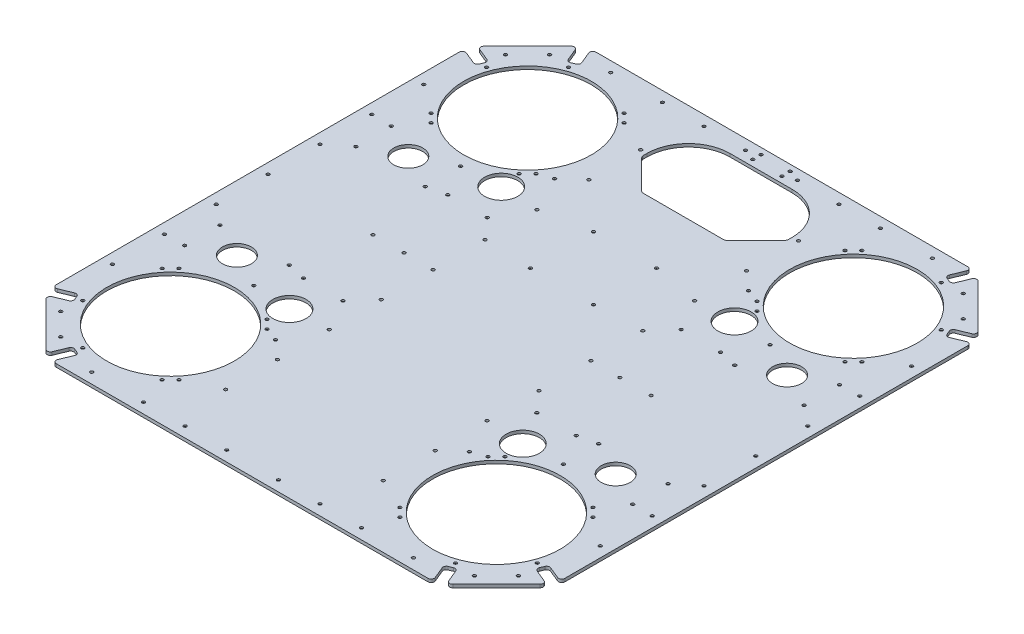
SolidWorks part; units mm, degrees
material "Thornel Mat VMA"
ref_plane "前视基准面" through (0, 0, 0) normal (0, 0, 1) x (1, 0, 0)
ref_plane "上视基准面" through (0, 0, 0) normal (0, 1, 0) x (1, 0, 0)
ref_plane "右视基准面" through (0, 0, 0) normal (1, 0, 0) x (0, 0, -1)
sketch "草图1" plane through (0, 0, 0) normal (0, 1, 0) x (1, 0, 0)
  line L1 (-245, -260) -> (245, -260)
  line L2 (-245, -260) -> (-245, 260)
  line L3 (-245, 260) -> (245, 260)
  line L4 (245, -260) -> (245, 260)
  line L5 (-245, -260) -> (245, 260) construction
  line L6 (-245, 260) -> (245, -260) construction
  point P0 (0, 0)
  dimension "D1" = 520
  dimension "D2" = 490
extrude "凸台-拉伸1" add sketch "草图1" along normal blind 3
sketch "草图2" plane through (0, 3, 0) normal (0, 1, 0) x (1, 0, 0)
  line L0 (-245, 0) -> (245, 0) construction
  line L1 (-245, 260) -> (-245, -260) construction
  line L2 (245, -260) -> (245, 260) construction
  line L3 (0, 260) -> (0, -260) construction
  line L4 (245, 260) -> (-245, 260) construction
  line L5 (-245, -260) -> (245, -260) construction
  line L6 (157, -172) -> (157, 172) construction
  line L7 (182.5, -82.5643) -> (215.9127, -65.5396) construction
  line L8 (145, -82.5643) -> (220, -82.5643) construction
  line L9 (157, -172) -> (203.669, -125.331) construction
  line L10 (157, -172) -> (199.424, -121.4411) construction
  line L11 (157, -172) -> (203.669, -218.669) construction
  line L12 (157, -172) -> (157, -260) construction
  line L13 (157, -172) -> (179.5733, -234.0197) construction
  line L14 (-157, -172) -> (-179.5733, -234.0197) construction
  line L15 (-157, -172) -> (-157, -260) construction
  line L16 (-157, -172) -> (-203.669, -218.669) construction
  line L17 (-157, -172) -> (-199.424, -121.4411) construction
  line L18 (-157, -172) -> (-203.669, -125.331) construction
  line L19 (-145, -82.5643) -> (-220, -82.5643) construction
  line L20 (-182.5, -82.5643) -> (-215.9127, -65.5396) construction
  line L21 (-157, -172) -> (-157, 172) construction
  line L22 (-182.5, 82.5643) -> (-215.9127, 65.5396) construction
  line L23 (-145, 82.5643) -> (-220, 82.5643) construction
  line L24 (-157, 172) -> (-203.669, 125.331) construction
  line L25 (-157, 172) -> (-199.424, 121.4411) construction
  line L26 (-157, 172) -> (-203.669, 218.669) construction
  line L27 (-157, 172) -> (-157, 260) construction
  line L28 (-157, 172) -> (-179.5733, 234.0197) construction
  line L29 (157, 172) -> (179.5733, 234.0197) construction
  line L30 (157, 172) -> (157, 260) construction
  line L31 (157, 172) -> (203.669, 218.669) construction
  line L32 (157, 172) -> (199.424, 121.4411) construction
  line L33 (157, 172) -> (203.669, 125.331) construction
  line L34 (145, 82.5643) -> (220, 82.5643) construction
  line L35 (182.5, 82.5643) -> (215.9127, 65.5396) construction
  line L36 (182.5, -45.0643) -> (182.5, -120.0643) construction
  circle A0 centre (157, -172) radius 61.5
  circle A1 centre (157, -172) radius 60 construction
  circle A2 centre (182.5, -82.5643) radius 33 construction
  circle A3 centre (182.5, -82.5643) radius 14
  circle A4 centre (182.5, -82.5643) radius 37.5 construction
  circle A5 centre (215.9127, -65.5396) radius 1.5
  circle A7 centre (215.9127, -99.5889) radius 1.5
  circle A9 centre (157, -172) radius 66 construction
  circle A10 centre (199.424, -121.4411) radius 1.5
  circle A11 centre (207.5589, -129.576) radius 1.5
  circle A14 centre (114.576, -222.5589) radius 1.5
  circle A15 centre (106.4411, -214.424) radius 1.5
  circle A16 centre (106.4411, -129.576) radius 1.5
  circle A17 centre (114.576, -121.4411) radius 1.5
  circle A18 centre (199.424, -222.5589) radius 1.5 [skipped]
  circle A19 centre (207.5589, -214.424) radius 1.5 [skipped]
  circle A20 centre (179.5733, -234.0197) radius 1.5
  circle A21 centre (219.0197, -194.5733) radius 1.5
  circle A22 centre (-157, -172) radius 66 construction
  circle A23 centre (-182.5, -82.5643) radius 37.5 construction
  circle A24 centre (-182.5, -82.5643) radius 33 construction
  circle A25 centre (-157, -172) radius 60 construction
  circle A26 centre (-219.0197, -194.5733) radius 1.5
  circle A27 centre (-179.5733, -234.0197) radius 1.5
  circle A28 centre (-114.576, -121.4411) radius 1.5
  circle A29 centre (-106.4411, -129.576) radius 1.5
  circle A30 centre (-106.4411, -214.424) radius 1.5
  circle A31 centre (-114.576, -222.5589) radius 1.5
  circle A32 centre (-207.5589, -129.576) radius 1.5
  circle A33 centre (-199.424, -121.4411) radius 1.5
  circle A35 centre (-215.9127, -99.5889) radius 1.5
  circle A37 centre (-215.9127, -65.5396) radius 1.5
  circle A38 centre (-182.5, -82.5643) radius 14
  circle A39 centre (-157, -172) radius 61.5
  circle A40 centre (-157, 172) radius 60 construction
  circle A41 centre (-182.5, 82.5643) radius 33 construction
  circle A42 centre (-182.5, 82.5643) radius 37.5 construction
  circle A43 centre (-157, 172) radius 66 construction
  circle A44 centre (157, 172) radius 66 construction
  circle A45 centre (182.5, 82.5643) radius 37.5 construction
  circle A46 centre (182.5, 82.5643) radius 33 construction
  circle A47 centre (157, 172) radius 60 construction
  circle A48 centre (-157, 172) radius 61.5
  circle A49 centre (-182.5, 82.5643) radius 14
  circle A50 centre (-215.9127, 65.5396) radius 1.5
  circle A52 centre (-215.9127, 99.5889) radius 1.5
  circle A54 centre (-199.424, 121.4411) radius 1.5
  circle A55 centre (-207.5589, 129.576) radius 1.5
  circle A56 centre (-114.576, 222.5589) radius 1.5
  circle A57 centre (-106.4411, 214.424) radius 1.5
  circle A58 centre (-106.4411, 129.576) radius 1.5
  circle A59 centre (-114.576, 121.4411) radius 1.5
  circle A60 centre (-179.5733, 234.0197) radius 1.5
  circle A61 centre (-219.0197, 194.5733) radius 1.5
  circle A62 centre (219.0197, 194.5733) radius 1.5
  circle A63 centre (179.5733, 234.0197) radius 1.5
  circle A64 centre (114.576, 121.4411) radius 1.5
  circle A65 centre (106.4411, 129.576) radius 1.5
  circle A66 centre (106.4411, 214.424) radius 1.5
  circle A67 centre (114.576, 222.5589) radius 1.5
  circle A68 centre (207.5589, 129.576) radius 1.5
  circle A69 centre (199.424, 121.4411) radius 1.5
  circle A71 centre (215.9127, 99.5889) radius 1.5
  circle A73 centre (215.9127, 65.5396) radius 1.5
  circle A74 centre (182.5, 82.5643) radius 14
  circle A75 centre (157, 172) radius 61.5
  circle A76 centre (149.0873, -99.5889) radius 1.5
  circle A77 centre (149.0873, -65.5396) radius 1.5
  circle A78 centre (-149.0873, -99.5889) radius 1.5
  circle A79 centre (-149.0873, -65.5396) radius 1.5
  circle A80 centre (149.0873, 99.5889) radius 1.5
  circle A81 centre (149.0873, 65.5396) radius 1.5
  circle A82 centre (-149.0873, 99.5889) radius 1.5
  circle A83 centre (-149.0873, 65.5396) radius 1.5
  circle A84 centre (112.4018, -102) radius 23 construction
  circle A85 centre (112.4018, -102) radius 16
  circle A86 centre (-112.4018, -102) radius 16
  circle A87 centre (112.4018, 102) radius 16
  circle A88 centre (-112.4018, 102) radius 16
  point P51 (157, -172)
  point P105 (-157, 0)
  point P121 (157, 0)
  dimension "D1" = 123
  dimension "D4" = 120
  dimension "D5" = 66
  dimension "D6" = 28
  dimension "D7" = 75
  dimension "D8" = 3
  dimension "D10" = 132
  dimension "D13" = 3
  dimension "D17" = 3
  dimension "D19" = 46
  dimension "D20" = 158
  dimension "D21" = 32
  dimension "D2" = 88
  dimension "D3" = 88
  dimension "D9" = 63
  dimension "D11" = 45
  dimension "D12" = 40
  dimension "D15" = 135
  dimension "D16" = 20
  dimension "D18" = 62.5
  dimension "D14" = 4
extrude "切除-拉伸1" cut sketch "草图2" against normal blind 4
chamfer "倒角1" distance 1.5 angle 45 48 edges at (-207.5589, 0, 128.076) (-199.424, 0, 119.9411) (-219.0197, 0, 193.0733) (-179.5733, 0, 232.5197) (-114.576, 0, 221.0589) (-106.4411, 0, 212.924) (-106.4411, 0, 128.076) (-114.576, 0, 119.9411) (-215.9127, 0, 64.0396) (-215.9127, 0, 98.0889) (-219.0197, 0, -196.0733) (-179.5733, 0, -235.5197) (-114.576, 0, -224.0589) (-106.4411, 0, -215.924) (-106.4411, 0, -131.076) (-114.576, 0, -122.9411) (-207.5589, 0, -131.076) (-199.424, 0, -122.9411) (-215.9127, 0, -101.0889) (-215.9127, 0, -67.0396) (207.5589, 0, -131.076) (199.424, 0, -122.9411) (219.0197, 0, -196.0733) (179.5733, 0, -235.5197) (114.576, 0, -224.0589) (106.4411, 0, -215.924) (106.4411, 0, -131.076) (114.576, 0, -122.9411) (215.9127, 0, -67.0396) (215.9127, 0, -101.0889) (215.9127, 0, 98.0889) (215.9127, 0, 64.0396) (106.4411, 0, 128.076) (114.576, 0, 119.9411) (199.424, 0, 119.9411) (207.5589, 0, 128.076) (179.5733, 0, 232.5197) (219.0197, 0, 193.0733) (106.4411, 0, 212.924) (114.576, 0, 221.0589) (-149.0873, 0, -67.0396) (-149.0873, 0, -101.0889) (149.0873, 0, -67.0396) (149.0873, 0, -101.0889) (149.0873, 0, 98.0889) (149.0873, 0, 64.0396) (-149.0873, 0, 98.0889) (-149.0873, 0, 64.0396)
chamfer "倒角2" distance 56 angle 45 4 edges at (-245, 1.5, 260) (245, 1.5, 260) (245, 1.5, -260) (-245, 1.5, -260)
sketch "草图3" plane through (0, 3, 0) normal (0, 1, 0) x (1, 0, 0)
  line L0 (0, -260) -> (0, 260) construction
  line L1 (-189, -260) -> (189, -260) construction
  line L2 (189, 260) -> (-189, 260) construction
  line L4 (-70, 165) -> (70, 165)
  line L5 (-70, 165) -> (-70, 240)
  line L6 (-70, 240) -> (70, 240)
  line L7 (70, 165) -> (70, 240)
  line L8 (-70, 165) -> (70, 240) construction
  line L9 (-70, 240) -> (70, 165) construction
  line L10 (-14, 246) -> (14, 246) construction
  line L11 (-14, 246) -> (-14, 254) construction
  line L12 (-14, 254) -> (14, 254) construction
  line L13 (14, 246) -> (14, 254) construction
  line L14 (-14, 246) -> (14, 254) construction
  line L15 (-14, 254) -> (14, 246) construction
  circle A0 centre (-14, 254) radius 1.5
  circle A1 centre (-14, 246) radius 1.5
  circle A2 centre (14, 246) radius 1.5
  circle A3 centre (14, 254) radius 1.5
  point P6 (0, 202.5)
  point P11 (0, 250)
  dimension "D7" = 3
  dimension "D8" = 3
  dimension "D1" = 20
  dimension "D2" = 140
  dimension "D3" = 75
  dimension "D4" = 6
  dimension "D5" = 8
  dimension "D6" = 28
extrude "切除-拉伸2" cut sketch "草图3" against normal through all
fillet "圆角1" radius 40 2 edges at (-70, 1.5, -240) (70, 1.5, -240)
chamfer "倒角3" distance 30 angle 45 2 edges at (70, 1.5, -165) (-70, 1.5, -165)
fillet "圆角2" radius 3 4 edges at (40, 1.5, -165) (70, 1.5, -195) (-40, 1.5, -165) (-70, 1.5, -195)
sketch "草图4" plane through (0, 3, 0) normal (0, 1, 0) x (1, 0, 0)
  line L0 (0, 260) -> (0, -260) construction
  line L3 (189, 260) -> (-189, 260) construction
  line L4 (-245, 204) -> (-245, -204) construction
  line L5 (-245, 0) -> (245, 0) construction
  line L6 (-189, -260) -> (189, -260) construction
  line L7 (-235, 0) -> (-235, 250) construction
  line L8 (-235, 250) -> (235, 250) construction
  line L9 (235, 0) -> (235, 250) construction
  circle A22 centre (-235, 50) radius 1.5
  circle A23 centre (-235, 100) radius 1.5
  circle A24 centre (-235, 150) radius 1.5
  circle A25 centre (-235, 200) radius 1.5
  circle A28 centre (-235, -200) radius 1.5
  circle A29 centre (-235, -150) radius 1.5
  circle A30 centre (-235, -100) radius 1.5
  circle A31 centre (-235, -50) radius 1.5
  circle A32 centre (-25, 250) radius 1.5
  circle A33 centre (-65, 250) radius 1.5
  circle A34 centre (-105, 250) radius 1.5
  circle A35 centre (-105, -250) radius 1.5
  circle A36 centre (-65, -250) radius 1.5
  circle A37 centre (-25, -250) radius 1.5
  circle A38 centre (25, -250) radius 1.5
  circle A39 centre (65, -250) radius 1.5
  circle A40 centre (105, -250) radius 1.5
  circle A41 centre (105, 250) radius 1.5
  circle A42 centre (65, 250) radius 1.5
  circle A43 centre (25, 250) radius 1.5
  circle A44 centre (235, -50) radius 1.5
  circle A45 centre (235, -100) radius 1.5
  circle A46 centre (235, -150) radius 1.5
  circle A47 centre (235, -200) radius 1.5
  circle A50 centre (235, 200) radius 1.5
  circle A51 centre (235, 150) radius 1.5
  circle A52 centre (235, 100) radius 1.5
  circle A53 centre (235, 50) radius 1.5
  circle A54 centre (-235, 250) radius 1.5 [skipped]
  circle A55 centre (-235, 0) radius 1.5
  circle A56 centre (235, 0) radius 1.5
  circle A57 centre (-155, 250) radius 1.5
  circle A58 centre (155, 250) radius 1.5
  circle A59 centre (155, -250) radius 1.5
  circle A60 centre (-155, -250) radius 1.5
  point P47 (0, 250)
  point P49 (0, 0)
  dimension "D4" = 3
  dimension "D8" = 3
  dimension "D5" = 3
  dimension "D1" = 10
  dimension "D2" = 10
  dimension "D3" = 50
  dimension "D7" = 5
  dimension "D6" = 25
  dimension "D9" = 3
  dimension "D10" = 2
extrude "切除-拉伸3" cut sketch "草图4" against normal through all
sketch "草图5" plane through (0, 3, 0) normal (0, 1, 0) x (1, 0, 0)
  line L0 (-217, 232) -> (-113.5129, 128.5129) construction
  line L1 (-189, 260) -> (-245, 204) construction
  line L2 (-189, 260) -> (-245, 204) construction
  line L5 (-181.9289, 252.9289) -> (-237.9289, 196.9289) construction
  line L6 (-245, 0) -> (245, 0) construction
  line L7 (-245, 204) -> (-245, -204) construction
  line L8 (245, -204) -> (245, 204) construction
  line L9 (0, 260) -> (0, -260) construction
  line L10 (189, 260) -> (-189, 260) construction
  line L11 (-189, -260) -> (189, -260) construction
  line L12 (181.9289, 252.9289) -> (237.9289, 196.9289) construction
  line L13 (189, 260) -> (245, 204) construction
  line L14 (217, 232) -> (113.5129, 128.5129) construction
  line L15 (217, -232) -> (113.5129, -128.5129) construction
  line L16 (189, -260) -> (245, -204) construction
  line L17 (181.9289, -252.9289) -> (237.9289, -196.9289) construction
  line L18 (-181.9289, -252.9289) -> (-237.9289, -196.9289) construction
  line L19 (-189, -260) -> (-245, -204) construction
  line L20 (-217, -232) -> (-113.5129, -128.5129) construction
  circle A2 centre (-157, 172) radius 61.5 construction
  circle A3 centre (-199.3223, 235.5355) radius 1.5
  circle A4 centre (-220.5355, 214.3223) radius 1.5
  circle A5 centre (220.5355, 214.3223) radius 1.5
  circle A6 centre (199.3223, 235.5355) radius 1.5
  circle A7 centre (199.3223, -235.5355) radius 1.5
  circle A8 centre (220.5355, -214.3223) radius 1.5
  circle A9 centre (-220.5355, -214.3223) radius 1.5
  circle A10 centre (-199.3223, -235.5355) radius 1.5
  dimension "D1" = 90
  dimension "D2" = 10
  dimension "D3" = 3
  dimension "D4" = 15
extrude "切除-拉伸4" cut sketch "草图5" against normal through all
chamfer "倒角4" distance 1.5 angle 45 42 edges at (-235, 0, 198.5) (-235, 0, 148.5) (-235, 0, 98.5) (-235, 0, 48.5) (-235, 0, 1.5) (-235, 0, -48.5) (-235, 0, -98.5) (-235, 0, -148.5) (-235, 0, -198.5) (-220.5355, 0, -215.8223) (-199.3223, 0, -234.0355) (-105, 0, -248.5) (-65, 0, -248.5) (-25, 0, -248.5) (25, 0, -251.5) (65, 0, -251.5) (105, 0, -251.5) (199.3223, 0, -237.0355) (220.5355, 0, -212.8223) (235, 0, -201.5) (235, 0, -151.5) (235, 0, -101.5) (235, 0, -51.5) (235, 0, -1.5) (235, 0, 51.5) (235, 0, 101.5) (235, 0, 151.5) (235, 0, 201.5) (220.5355, 0, 212.8223) (199.3223, 0, 237.0355) (105, 0, 251.5) (65, 0, 251.5) (25, 0, 251.5) (-25, 0, 248.5) (-65, 0, 248.5) (-105, 0, 248.5) (-220.5355, 0, 215.8223) (-199.3223, 0, 234.0355) (14, 0, -255.5) (14, 0, -247.5) (-14, 0, -244.5) (-14, 0, -252.5)
sketch "草图6" plane through (0, 0, 0) normal (0, -1, 0) x (1, 0, 0)
  line L0 (-245, 204) -> (-172.5761, 174.0011) construction
  line L1 (-245, -204) -> (-245, 204) construction
  line L3 (-263.0882, 206.0804) -> (-226.5881, 190.9616)
  line L4 (-259.2614, 215.3192) -> (-222.7612, 200.2004)
  line L5 (-245, 204) -> (-228.7796, 197.2813) construction
  line L6 (-243.0866, 208.6194) -> (-226.8662, 201.9007) construction
  line L7 (-246.9134, 199.3806) -> (-230.693, 192.6619) construction
  line L8 (-222.7612, 200.2004) -> (-226.5881, 190.9616)
  line L9 (-263.0882, 206.0804) -> (-259.2614, 215.3192)
  line L10 (0, 260) -> (0, -260) construction
  line L11 (-189, 260) -> (189, 260) construction
  line L12 (189, -260) -> (-189, -260) construction
  line L13 (-245, 0) -> (245, 0) construction
  line L14 (245, 204) -> (245, -204) construction
  line L15 (-217, 232) -> (-113.5129, 128.5129) construction
  line L16 (-189, 260) -> (-245, 204) construction
  line L17 (-191.0804, 278.0882) -> (-175.9616, 241.5881)
  line L18 (-185.2004, 237.7612) -> (-175.9616, 241.5881)
  line L19 (-200.3192, 274.2614) -> (-185.2004, 237.7612)
  line L20 (-191.0804, 278.0882) -> (-200.3192, 274.2614)
  line L21 (263.0882, 206.0804) -> (226.5881, 190.9616)
  line L22 (222.7612, 200.2004) -> (226.5881, 190.9616)
  line L23 (259.2614, 215.3192) -> (222.7612, 200.2004)
  line L24 (263.0882, 206.0804) -> (259.2614, 215.3192)
  line L25 (191.0804, 278.0882) -> (200.3192, 274.2614)
  line L26 (200.3192, 274.2614) -> (185.2004, 237.7612)
  line L27 (185.2004, 237.7612) -> (175.9616, 241.5881)
  line L28 (191.0804, 278.0882) -> (175.9616, 241.5881)
  line L29 (191.0804, -278.0882) -> (175.9616, -241.5881)
  line L30 (185.2004, -237.7612) -> (175.9616, -241.5881)
  line L31 (200.3192, -274.2614) -> (185.2004, -237.7612)
  line L32 (191.0804, -278.0882) -> (200.3192, -274.2614)
  line L33 (263.0882, -206.0804) -> (259.2614, -215.3192)
  line L34 (259.2614, -215.3192) -> (222.7612, -200.2004)
  line L35 (222.7612, -200.2004) -> (226.5881, -190.9616)
  line L36 (263.0882, -206.0804) -> (226.5881, -190.9616)
  line L37 (-217, -232) -> (-113.5129, -128.5129) construction
  line L38 (-245, -204) -> (-172.5761, -174.0011) construction
  line L39 (-191.0804, -278.0882) -> (-200.3192, -274.2614)
  line L40 (-200.3192, -274.2614) -> (-185.2004, -237.7612)
  line L41 (-185.2004, -237.7612) -> (-175.9616, -241.5881)
  line L42 (-191.0804, -278.0882) -> (-175.9616, -241.5881)
  line L43 (-263.0882, -206.0804) -> (-259.2614, -215.3192)
  line L44 (-222.7612, -200.2004) -> (-226.5881, -190.9616)
  line L45 (-259.2614, -215.3192) -> (-222.7612, -200.2004)
  line L46 (-263.0882, -206.0804) -> (-226.5881, -190.9616)
  circle A0 centre (-157, 172) radius 61.5 construction
  dimension "D1" = 67.5
  dimension "D4" = 22
  dimension "D5" = 90
  dimension "D2" = 5
  dimension "D3" = 5
extrude "切除-拉伸5" cut sketch "草图6" against normal blind 3
fillet "圆角3" radius 3 32 edges at (-245, 1.5, 198.588) (-241.1732, 1.5, 207.8268) (-226.5881, 1.5, 190.9616) (-222.7612, 1.5, 200.2004) (-245, 1.5, -198.588) (-241.1732, 1.5, -207.8268) (-222.7612, 1.5, -200.2004) (-226.5881, 1.5, -190.9616) (-183.588, 1.5, -260) (-192.8268, 1.5, -256.1732) (-175.9616, 1.5, -241.5881) (-185.2004, 1.5, -237.7612) (183.588, 1.5, -260) (192.8268, 1.5, -256.1732) (185.2004, 1.5, -237.7612) (175.9616, 1.5, -241.5881) (241.1732, 1.5, -207.8268) (245, 1.5, -198.588) (222.7612, 1.5, -200.2004) (226.5881, 1.5, -190.9616) (241.1732, 1.5, 207.8268) (245, 1.5, 198.588) (226.5881, 1.5, 190.9616) (222.7612, 1.5, 200.2004) (192.8268, 1.5, 256.1732) (183.588, 1.5, 260) (175.9616, 1.5, 241.5881) (185.2004, 1.5, 237.7612) (-183.588, 1.5, 260) (-192.8268, 1.5, 256.1732) (-175.9616, 1.5, 241.5881) (-185.2004, 1.5, 237.7612)
sketch "草图7" plane through (0, 3, 0) normal (0, 1, 0) x (1, 0, 0)
  line L0 (131.4018, 102) -> (93.4018, 102) construction
  line L1 (131.4018, 134.5) -> (93.4018, 134.5) construction
  line L2 (131.4018, 134.5) -> (131.4018, 69.5) construction
  line L3 (131.4018, 69.5) -> (93.4018, 69.5) construction
  line L4 (93.4018, 134.5) -> (93.4018, 69.5) construction
  line L5 (131.4018, 134.5) -> (93.4018, 69.5) construction
  line L6 (131.4018, 69.5) -> (93.4018, 134.5) construction
  line L7 (0, 260) -> (0, -260) construction
  line L8 (179.0982, 260) -> (-179.0982, 260) construction
  line L9 (-179.0982, -260) -> (179.0982, -260) construction
  line L10 (245, 0) -> (-245, 0) construction
  line L11 (245, -194.0982) -> (245, 194.0982) construction
  line L12 (-245, 194.0982) -> (-245, -194.0982) construction
  line L13 (131.4018, -69.5) -> (93.4018, -134.5) construction
  line L14 (131.4018, -134.5) -> (93.4018, -69.5) construction
  line L15 (93.4018, -134.5) -> (93.4018, -69.5) construction
  line L16 (131.4018, -69.5) -> (93.4018, -69.5) construction
  line L17 (131.4018, -134.5) -> (131.4018, -69.5) construction
  line L18 (131.4018, -134.5) -> (93.4018, -134.5) construction
  line L19 (131.4018, -102) -> (93.4018, -102) construction
  circle A0 centre (131.4018, 69.5) radius 1.5
  circle A1 centre (93.4018, 69.5) radius 1.5
  circle A2 centre (93.4018, 134.5) radius 1.5
  circle A3 centre (-93.4018, 134.5) radius 1.5
  circle A4 centre (-93.4018, 69.5) radius 1.5
  circle A5 centre (-131.4018, 69.5) radius 1.5
  circle A6 centre (-131.4018, -69.5) radius 1.5
  circle A7 centre (-93.4018, -69.5) radius 1.5
  circle A8 centre (-93.4018, -134.5) radius 1.5
  circle A9 centre (93.4018, -134.5) radius 1.5
  circle A10 centre (93.4018, -69.5) radius 1.5
  circle A11 centre (131.4018, -69.5) radius 1.5
  point P0 (112.4018, 102)
  point P44 (112.4018, -102)
  dimension "D3" = 3
  dimension "D4" = 3
  dimension "D1" = 38
  dimension "D2" = 65
extrude "切除-拉伸6" cut sketch "草图7" against normal blind 3
sketch "草图8" plane through (0, 3, 0) normal (0, 1, 0) x (1, 0, 0)
  line L0 (0, 260) -> (0, -260) construction
  line L1 (179.0982, 260) -> (-179.0982, 260) construction
  line L2 (-179.0982, -260) -> (179.0982, -260) construction
  line L4 (-30.4, 48.1) -> (30.4, 48.1) construction
  line L5 (-30.4, 48.1) -> (-30.4, 108.9) construction
  line L6 (-30.4, 108.9) -> (30.4, 108.9) construction
  line L7 (30.4, 48.1) -> (30.4, 108.9) construction
  line L8 (-30.4, 48.1) -> (30.4, 108.9) construction
  line L9 (-30.4, 108.9) -> (30.4, 48.1) construction
  circle A0 centre (-30.4, 108.9) radius 1.5
  circle A1 centre (-30.4, 48.1) radius 1.5
  circle A2 centre (30.4, 48.1) radius 1.5
  circle A3 centre (30.4, 108.9) radius 1.5
  point P6 (0, 78.5)
  dimension "D4" = 3
  dimension "D5" = 3
  dimension "D1" = 181.5
  dimension "D2" = 60.8
  dimension "D3" = 60.8
extrude "切除-拉伸7" cut sketch "草图8" against normal through all both and the other way through all
chamfer "倒角5" distance 1.5 angle 45 16 edges at (-131.4018, 0, 71) (-93.4018, 0, 71) (-93.4018, 0, 133) (93.4018, 0, 136) (93.4018, 0, 68) (131.4018, 0, 68) (93.4018, 0, -68) (131.4018, 0, -68) (93.4018, 0, -136) (-93.4018, 0, -133) (-131.4018, 0, -71) (-93.4018, 0, -71) (-30.4, 0, -46.6) (30.4, 0, -49.6) (-30.4, 0, -107.4) (30.4, 0, -110.4)
sketch "草图9" plane through (0, 3, 0) normal (0, 1, 0) x (1, 0, 0)
  line L0 (-245, 0) -> (245, 0) construction
  line L1 (-245, 194.0982) -> (-245, -194.0982) construction
  line L2 (245, -194.0982) -> (245, 194.0982) construction
  line L3 (0, 260) -> (0, -260) construction
  line L4 (179.0982, 260) -> (-179.0982, 260) construction
  line L5 (-179.0982, -260) -> (179.0982, -260) construction
  circle A0 centre (-104, 0) radius 1.5
  circle A1 centre (-134, 0) radius 1.5
  circle A2 centre (134, 0) radius 1.5
  circle A3 centre (104, 0) radius 1.5
  dimension "D1" = 3
  dimension "D2" = 104
  dimension "D3" = 3
  dimension "D4" = 30
extrude "切除-拉伸8" cut sketch "草图9" against normal through all
sketch "草图10" plane through (0, 3, 0) normal (0, 1, 0) x (1, 0, 0)
  line L0 (0, 260) -> (0, -260) construction
  line L1 (179.0982, 260) -> (-179.0982, 260) construction
  line L2 (-179.0982, -260) -> (179.0982, -260) construction
  line L3 (-76, 260) -> (-76, -260) construction
  line L4 (76, 260) -> (76, -260) construction
  line L5 (0, 0) -> (-245, 0) construction
  line L6 (-245, 194.0982) -> (-245, -194.0982) construction
  circle A0 centre (-76, 0) radius 1.5
  circle A1 centre (-76, 50) radius 1.5
  circle A2 centre (-76, 100) radius 1.5
  circle A3 centre (-76, 150) radius 1.5
  circle A4 centre (-76, 200) radius 1.5
  circle A5 centre (-76, -200) radius 1.5
  circle A6 centre (-76, -150) radius 1.5
  circle A7 centre (-76, -100) radius 1.5
  circle A8 centre (-76, -50) radius 1.5
  circle A9 centre (76, -50) radius 1.5
  circle A10 centre (76, -100) radius 1.5
  circle A11 centre (76, -150) radius 1.5
  circle A12 centre (76, -200) radius 1.5
  circle A13 centre (76, 200) radius 1.5
  circle A14 centre (76, 150) radius 1.5
  circle A15 centre (76, 100) radius 1.5
  circle A16 centre (76, 50) radius 1.5
  circle A17 centre (76, 0) radius 1.5
  dimension "D2" = 3
  dimension "D3" = 5
  dimension "D1" = 76
extrude "切除-拉伸9" cut sketch "草图10" against normal through all
